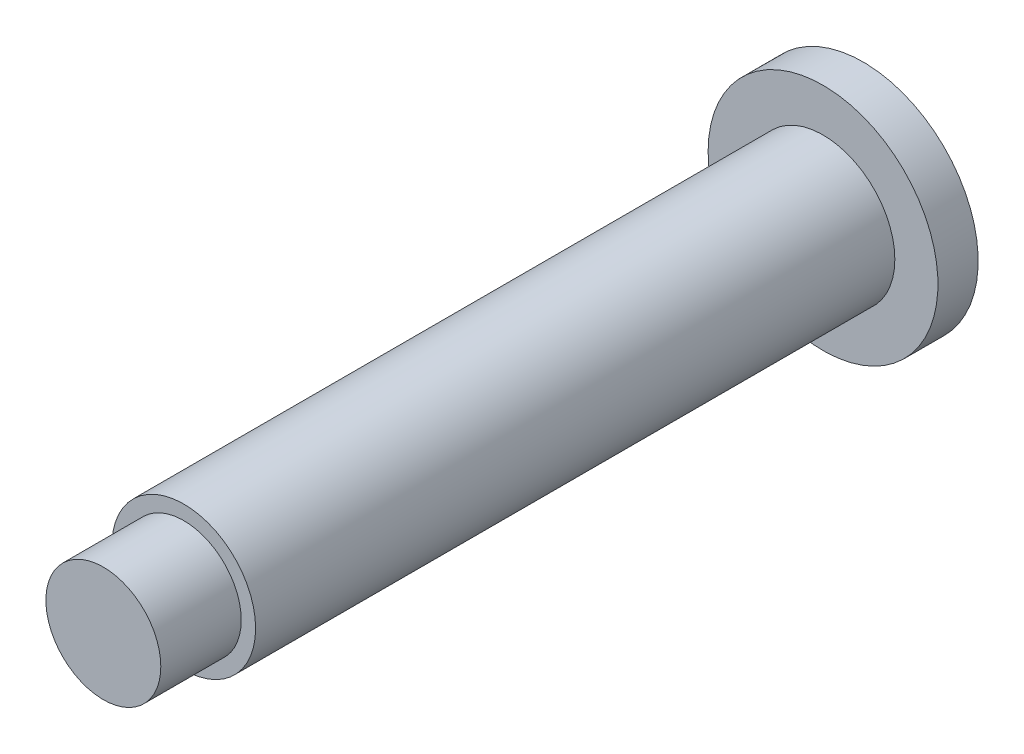
SolidWorks part; units mm, degrees
ref_plane "Front Plane" through (0, 0, 0) normal (1, 0, 0) x (0, 1, 0)
ref_plane "Top Plane" through (0, 0, 0) normal (0, 0, 1) x (0, 1, 0)
ref_plane "Right Plane" through (0, 0, 0) normal (0, 1, 0) x (-1, 0, 0)
sketch "Sketch1" plane through (0, 0, 0) normal (0, 0, 1) x (0, 1, 0)
  circle A0 centre (0, 0) radius 2.5
  dimension "D1" = 5
extrude "Boss-Extrude1" add sketch "Sketch1" along normal blind 22.25 contours A0
sketch "Sketch2" plane through (0, 0, 0) normal (0, 0, -1) x (1, 0, 0)
  circle A0 centre (0, 0) radius 4
  dimension "D1" = 8
extrude "Boss-Extrude2" add sketch "Sketch2" along normal blind 1.4
sketch "Sketch3" plane through (0, 0, -1.4) normal (0, 0, -1) x (1, 0, 0)
  circle A0 centre (0, 0) radius 2.05
  dimension "D1" = 4.1
extrude "Cut-Extrude1" cut sketch "Sketch3" against normal blind 3
sketch "Sketch4" plane through (0, 0, 22.25) normal (0, 0, 1) x (1, 0, 0)
  circle A0 centre (0, 0) radius 2
extrude "Boss-Extrude3" add sketch "Sketch4" along normal blind 2.8
equation "\"whitekey_cutout_length\"= 101.5"
equation "\"key_mount_recess_length\"=50"
equation "\"key_mount_recess_height\"=12.5"
equation "\"key_mount_recess_depth\"=1.5"
equation "\"wall_thickness\"=10"
equation "\"guide_brace_height\"=20"
equation "\"guide_brace_thickness\"=2"
equation "\"dowel_recess_depth\"=10"
equation "\"dowel_recess_offset\"=3.25"
equation "\"base_mount_height\"=40"
equation "\"base_rear_length\"=80"
equation "\"base_front_length\"=111.5"
equation "\"screw_hole_wall_offset\"=7.25"
equation "\"screw_hole_edge_inset\"=\"dowel_recess_depth\"/2"
equation "\"screw_hole_diameter\"=3.8"
equation "\"screw_head_hole_diameter\"=6.7"
equation "\"screw_nut_hole_side_len\"=3.5"
equation "\"screw_nut_recess_offset\"=0.35"
equation "\"screw_head_and_nut_recess_depth\"=2.5"
equation "\"screw_shaft_diameter\"=3.5"
equation "\"switch_board_width\"=30"
equation "\"switch_board_wall_offset\"=11.5"
equation "\"heatset_insert_hole_diameter\"=4.8"
equation "\"heatset_insert_hole_depth\"=3.8"
equation "\"front_rear_panel_width\"=23.75"
equation "\"rod_length_adj\"=0.5"
equation "\"rod_insert_length\"=2.8"
equation "\"D1@Boss-Extrude1\"=\"rod_length_adj\"+21.75mm"
equation "\"D1@Boss-Extrude2\"=2-\"rod_length_adj\"-0.1"
equation "\"D1@Boss-Extrude3\"=\"rod_insert_length\""
equation "\"switch_board_thickness\"=1.6"
equation "\"rod_diameter\"=5"
equation "\"rod_head_diameter\"=8"
equation "\"switch_black_key_mount_height\"=8"
equation "\"switch_white_key_mount_height\"=3"
equation "\"D1@Sketch1\"=\"rod_diameter\""
equation "\"D1@Sketch2\"=\"rod_head_diameter\""
equation "\"D1@Sketch3\"=\"rod_diameter\"-1+0.1"
equation "\"D1@Sketch4\"=\"rod_diameter\"-1"
